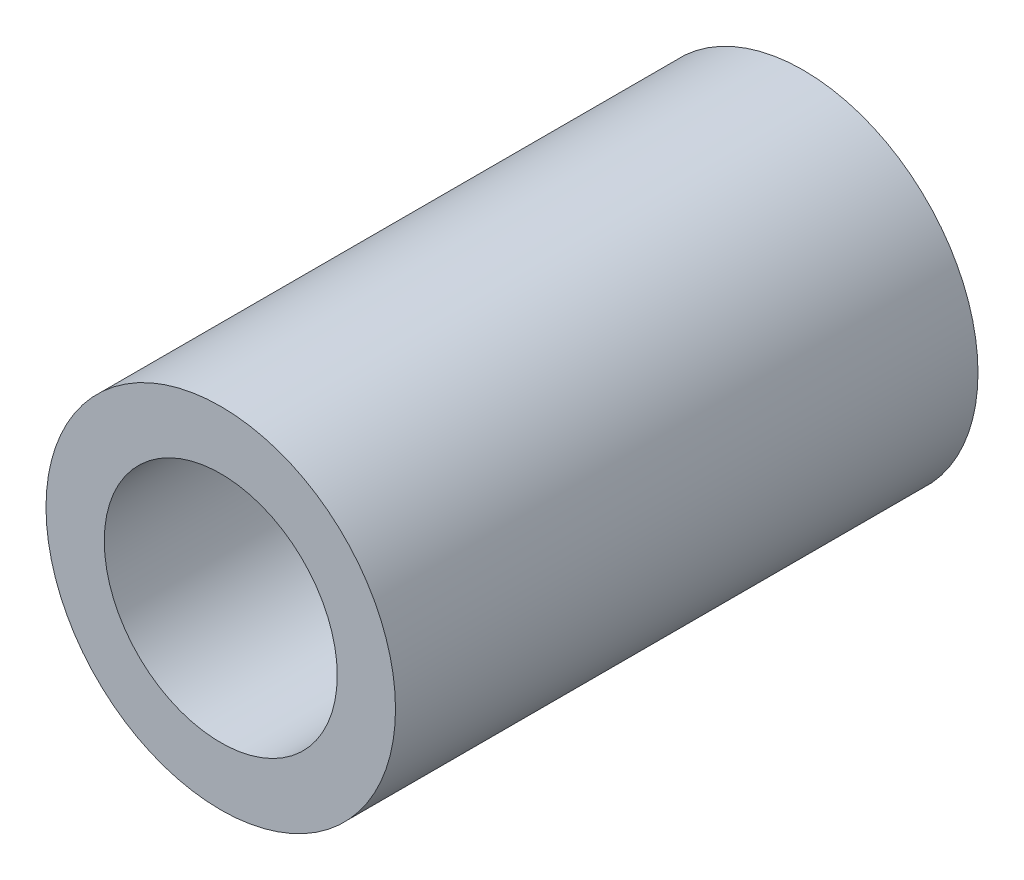
SolidWorks part; units mm, degrees
ref_plane "Front" through (0, 0, 0) normal (0, 0, 1) x (1, 0, 0)
ref_plane "Top" through (0, 0, 0) normal (0, 1, 0) x (1, 0, 0)
ref_plane "Right" through (0, 0, 0) normal (1, 0, 0) x (0, 0, -1)
sketch "Sketch1" plane through (0, 0, 0) normal (0, 0, 1) x (1, 0, 0)
  circle A0 centre (0, 0) radius 2.54
  circle A1 centre (0, 0) radius 3.81
  dimension "D1" = 5.08
  dimension "D2" = 7.62
extrude "Boss-Extrude1" add sketch "Sketch1" along normal blind 12.7
extrude "Boss-Extrude2" add sketch "Sketch1<2>" along normal blind 2.54 contours A0 region at (0, 0, 0)
sketch "Sketch1<2>" plane through (0, 0, 0) normal (0, 0, 1) x (1, 0, 0) same geometry as "Sketch1"
